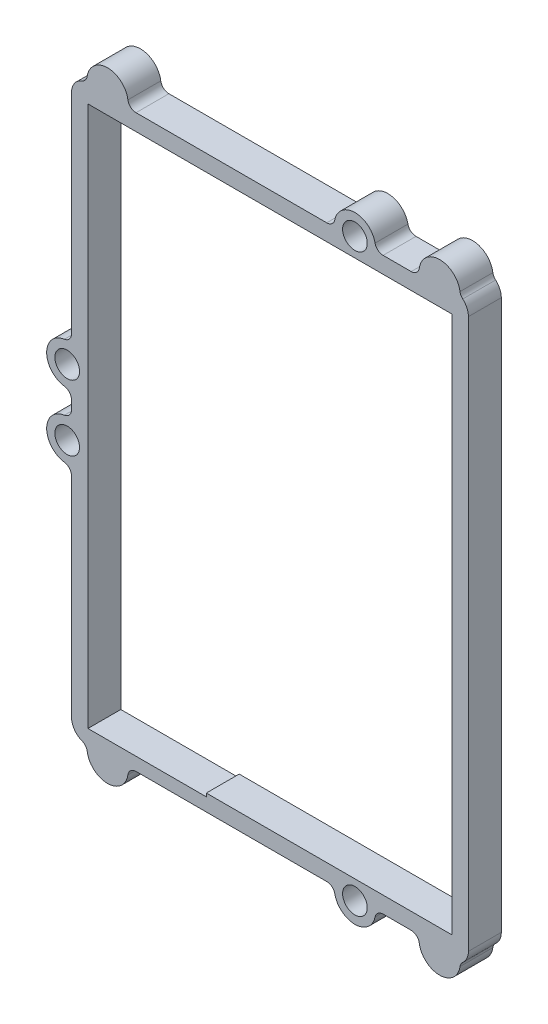
SolidWorks part; units mm, degrees
ref_plane "Front Plane" through (0, 0, 0) normal (1, 0, 0) x (0, 1, 0)
ref_plane "Top Plane" through (0, 0, 0) normal (0, 0, 1) x (0, 1, 0)
ref_plane "Right Plane" through (0, 0, 0) normal (0, 1, 0) x (-1, 0, 0)
ref_axis "x axis" through (-88.99, 0, 0) along (1, 0, 0)
ref_axis "y xxis" through (0, 88.99, 0) along (0, -1, 0)
ref_axis "z axis" through (0, 0, 55) along (0, 0, -1)
sketch "Plate holes" plane through (0, 0, 0) normal (0, 0, 1) x (0, 1, 0)
  line L0 (-4, 0) -> (4, 0) construction
  line L1 (-17.5, -17.5) -> (17.5, -17.5) construction
  line L2 (-17.5, -17.5) -> (-17.5, 17.5) construction
  line L3 (-17.5, 17.5) -> (17.5, 17.5) construction
  line L4 (17.5, -17.5) -> (17.5, 17.5) construction
  line L5 (-17.5, -17.5) -> (17.5, 17.5) construction
  line L6 (-17.5, 17.5) -> (17.5, -17.5) construction
  line L7 (-35, -35) -> (35, -35) construction
  line L8 (-35, -35) -> (-35, 35) construction
  line L9 (-35, 35) -> (35, 35) construction
  line L10 (35, -35) -> (35, 35) construction
  line L11 (-35, -35) -> (35, 35) construction
  line L12 (-35, 35) -> (35, -35) construction
  circle A0 centre (-35, 35) radius 1 construction
  circle A1 centre (-17.5, 17.5) radius 1 construction
  circle A2 centre (17.5, 17.5) radius 1 construction
  circle A3 centre (35, 35) radius 1 construction
  circle A4 centre (-35, -35) radius 1 construction
  circle A6 centre (-17.5, -17.5) radius 1 construction
  circle A7 centre (17.5, -17.5) radius 1 construction
  circle A8 centre (35, -35) radius 1 construction
  circle A9 centre (-4, 0) radius 1 construction
  circle A10 centre (4, 0) radius 1 construction
  point P0 (0, 0)
  point P5 (0, 0)
  point P21 (0, 0)
  dimension "D3" = 2
  dimension "D4" = 8
  dimension "D1" = 35
  dimension "D2" = 70
sketch "PCB holes" plane through (0, 0, 0) normal (0, 0, 1) x (0, 1, 0)
  line L0 (-35.2, -4.9073) -> (35.2, -4.9073) construction
  line L1 (35.2, -4.9073) -> (35.2, -45.3073) construction
  line L2 (35.2, -45.3073) -> (-35.2, -45.3073) construction
  line L3 (-35.2, -45.3073) -> (-35.2, -4.9073) construction
  line L4 (-35.2, -4.9073) -> (35.2, -45.3073) construction
  line L5 (35.2, -4.9073) -> (-35.2, -45.3073) construction
  circle A0 centre (-35.2, -4.9073) radius 1 construction
  circle A1 centre (35.2, -4.9073) radius 1 construction
  circle A2 centre (35.2, -45.3073) radius 1 construction
  circle A3 centre (-35.2, -45.3073) radius 1 construction
  point P7 (0, -25.1073)
  dimension "D1" = 40.4
  dimension "D3" = 2
  dimension "D2" = 70.4
sketch "Sketch3" plane through (0, 0, 0) normal (0, 0, 1) x (0, 1, 0)
  line L10 (-32.7, -9.8803) -> (-32.7, -46.8073)
  line L11 (-32.7, -46.8073) -> (32.7, -46.8073)
  line L12 (32.7, -46.8073) -> (32.7, -2.521)
  line L13 (32.7, -2.521) -> (-32.7, -2.521)
  line L14 (-32.7, -2.521) -> (-32.7, -9.8803)
  line L15 (-34.7, -0.521) -> (-34.7, -2.4578)
  line L16 (-7.5047, -2.521) -> (-7.5047, 2.479) construction
  line L17 (-34.7, -9.8803) -> (-34.7, -32.5181)
  line L18 (12.7907, -51.8073) -> (12.7907, -46.8073) construction
  line L19 (-34.7, -48.8073) -> (34.7, -48.8073)
  line L20 (34.7, -48.8073) -> (34.7, -47.7568)
  line L21 (34.7, -0.521) -> (6.4451, -0.521)
  line L22 (-34.7, -47.7568) -> (-34.7, -48.8073)
  line L23 (-34.7, -9.8803) -> (-34.7, -48.8073) construction
  line L24 (-34.7, -37.4819) -> (-34.7, -42.8578)
  line L25 (-34.7, -7.3568) -> (-34.7, -9.8803)
  line L26 (-34.7, -0.521) -> (-34.7, -9.8803) construction
  line L27 (-6.4451, -0.521) -> (-34.7, -0.521)
  line L28 (34.7, -0.521) -> (-34.7, -0.521) construction
  line L29 (1.5549, -0.521) -> (-1.5549, -0.521)
  line L30 (34.7, -2.4578) -> (34.7, -0.521)
  line L31 (34.7, -48.8073) -> (34.7, -0.521) construction
  line L32 (34.7, -32.5181) -> (34.7, -7.3568)
  line L33 (34.7, -42.8578) -> (34.7, -37.4819)
  arc A1 (-34.7, -2.4578) -> (-34.7, -7.3568) centre (-35.2, -4.9073) ccw
  arc A2 (-34.7, -32.5181) -> (-34.7, -37.4819) centre (-35, -35) ccw
  arc A3 (-34.7, -42.8578) -> (-34.7, -47.7568) centre (-35.2, -45.3073) ccw
  arc A4 (34.7, -47.7568) -> (34.7, -42.8578) centre (35.2, -45.3073) ccw
  arc A5 (34.7, -37.4819) -> (34.7, -32.5181) centre (35, -35) ccw
  arc A6 (34.7, -7.3568) -> (34.7, -2.4578) centre (35.2, -4.9073) ccw
  arc A7 (-1.5549, -0.521) -> (-6.4451, -0.521) centre (-4, 0) ccw
  arc A8 (6.4451, -0.521) -> (1.5549, -0.521) centre (4, 0) ccw
  dimension "D1" = 5
  dimension "D2" = 5
  dimension "D3" = 2
  dimension "D4" = 1.5
extrude "Boss-Extrude1" add sketch "Sketch3" along normal blind 4
sketch "Sketch4" plane through (0, 0, 4) normal (0, 0, 1) x (1, 0, 0)
  circle A0 centre (0, 4) radius 1.5
  circle A1 centre (0, -4) radius 1.5
  circle A2 centre (35, -35) radius 1.5
  circle A3 centre (35, 35) radius 1.5
  dimension "D1" = 3
extrude "Cut-Extrude1" cut sketch "Sketch4" against normal blind 3
sketch "Sketch5" plane through (0, 0, 0) normal (0, 0, -1) x (1, 0, 0)
  circle A0 centre (4.9073, 35.2) radius 1.5
  circle A1 centre (45.3073, 35.2) radius 1.5
  circle A2 centre (45.3073, -35.2) radius 1.5
  circle A3 centre (4.9073, -35.2) radius 1.5
  dimension "D1" = 3
extrude "Cut-Extrude2" cut sketch "Sketch5" against normal blind 3
sketch "Sketch6" plane through (0, 0, 4) normal (0, 0, 1) x (1, 0, 0)
  line L0 (2.521, -32.7) -> (2.521, -33.1)
  line L1 (2.521, -33.1) -> (16.921, -33.1)
  line L2 (16.921, -33.1) -> (16.921, -32.7)
  line L4 (16.921, -32.7) -> (2.521, -32.7)
  line L5 (2.521, -32.7) -> (46.8073, -32.7) construction
  point P3 (0, 0)
  point P6 (16.921, -32.7)
  point P8 (2.521, -32.7)
  point P10 (0, 0)
  dimension "D1" = 14.4
  dimension "D2" = 0.4
extrude "Cut-Extrude3" cut sketch "Sketch6" against normal up to surface (4 mm away) up to face at (3.4073, 35.2, 0)
fillet "Fillet1" radius 1 16 edges at (0.521, -6.4451, 2) (0.521, 6.4451, 2) (0.521, 1.5549, 2) (0.521, -1.5549, 2) (7.3568, 34.7, 2) (2.4578, 34.7, 2) (32.5181, 34.7, 2) (37.4819, 34.7, 2) (42.8578, 34.7, 2) (47.7568, 34.7, 2) (47.7568, -34.7, 2) (42.8578, -34.7, 2) (32.5181, -34.7, 2) (37.4819, -34.7, 2) (2.4578, -34.7, 2) (7.3568, -34.7, 2)
fillet "Fillet2" radius 2 4 edges at (0.521, 34.7, 2) (48.8073, 34.7, 2) (48.8073, -34.7, 2) (0.521, -34.7, 2)
